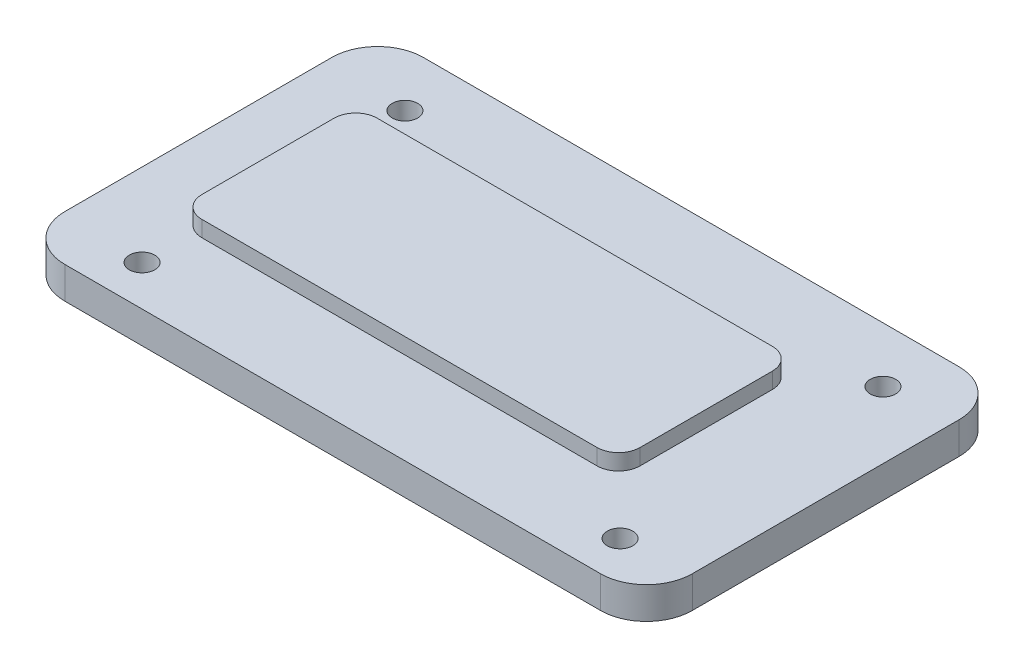
SolidWorks part; units mm, degrees
ref_plane "Front Plane" through (0, 0, 0) normal (0, 0, 1) x (1, 0, 0)
ref_plane "Top Plane" through (0, 0, 0) normal (0, 1, 0) x (1, 0, 0)
ref_plane "Right Plane" through (0, 0, 0) normal (1, 0, 0) x (0, 0, -1)
sketch "Sketch1" plane through (0, 0, 0) normal (0, 1, 0) x (1, 0, 0)
  line L0 (21.25, -8.375) -> (21.25, 8.375)
  line L1 (18.375, 11.25) -> (-15.25, 11.25)
  line L2 (-18.125, 8.375) -> (-18.125, -8.375)
  line L3 (-15.25, -11.25) -> (18.375, -11.25)
  line L4 (-15.25, -11.5) -> (18.375, -11.5)
  line L5 (-18.375, 8.375) -> (-18.375, -8.375)
  line L6 (18.375, 11.5) -> (-15.25, 11.5)
  line L7 (21.5, -8.375) -> (21.5, 8.375)
  line L8 (-15.25, -11.5) -> (18.375, -11.5) construction
  line L9 (-18.375, 8.375) -> (-18.375, -8.375) construction
  line L10 (18.375, 11.5) -> (-15.25, 11.5) construction
  line L11 (21.5, -8.375) -> (21.5, 8.375) construction
  arc A0 (21.25, 8.375) -> (18.375, 11.25) centre (18.375, 8.375) ccw
  arc A1 (-15.25, 11.25) -> (-18.125, 8.375) centre (-15.25, 8.375) ccw
  arc A2 (-18.125, -8.375) -> (-15.25, -11.25) centre (-15.25, -8.375) ccw
  arc A3 (18.375, -11.25) -> (21.25, -8.375) centre (18.375, -8.375) ccw
  arc A4 (-18.375, -8.375) -> (-15.25, -11.5) centre (-15.25, -8.375) ccw
  arc A5 (-15.25, 11.5) -> (-18.375, 8.375) centre (-15.25, 8.375) ccw
  arc A6 (21.5, 8.375) -> (18.375, 11.5) centre (18.375, 8.375) ccw
  arc A7 (18.375, -11.5) -> (21.5, -8.375) centre (18.375, -8.375) ccw
  arc A8 (-18.375, -8.375) -> (-15.25, -11.5) centre (-15.25, -8.375) ccw construction
  arc A9 (-15.25, 11.5) -> (-18.375, 8.375) centre (-15.25, 8.375) ccw construction
  arc A10 (21.5, 8.375) -> (18.375, 11.5) centre (18.375, 8.375) ccw construction
  arc A11 (18.375, -11.5) -> (21.5, -8.375) centre (18.375, -8.375) ccw construction
  dimension "D1" = 0
  dimension "D2" = 0.25
extrude "Boss-Extrude1" add sketch "Sketch1" along normal blind 3
sketch "Sketch2" plane through (0, 3, 0) normal (0, 1, 0) x (1, 0, 0)
  line L0 (14, -4.15) -> (14, 4.15) construction
  line L1 (12.4, 5.75) -> (-12.4, 5.75) construction
  line L2 (18.375, 11.5) -> (-15.25, 11.5) construction
  line L3 (24.5, 12.5) -> (-21.375, 12.5)
  line L4 (21.25, -8.375) -> (21.25, 8.375)
  line L5 (18.375, 11.25) -> (-15.25, 11.25)
  line L6 (-18.125, 8.375) -> (-18.125, -8.375)
  line L7 (-15.25, -11.25) -> (18.375, -11.25)
  line L8 (21.25, -8.375) -> (21.25, 8.375)
  line L9 (18.375, 11.25) -> (-15.25, 11.25)
  line L10 (-18.125, 8.375) -> (-18.125, -8.375)
  line L11 (-15.25, -11.25) -> (18.375, -11.25)
  line L12 (-24.5, 9.375) -> (-24.5, -9.375)
  line L13 (-21.375, -12.5) -> (24.5, -12.5)
  line L14 (24.5, 12.5) -> (-21.375, 12.5)
  line L15 (-24.5, 9.375) -> (-24.5, -9.375)
  line L16 (-21.375, -12.5) -> (24.5, -12.5)
  line L17 (-12.4, -5.75) -> (12.4, -5.75) construction
  line L18 (-14, 4.15) -> (-14, -4.15) construction
  line L19 (14, -4.15) -> (14, 4.15) construction
  line L20 (12.4, 5.75) -> (-12.4, 5.75) construction
  line L21 (18.375, 11.5) -> (-15.25, 11.5)
  line L22 (-12.4, -5.75) -> (12.4, -5.75) construction
  line L23 (-14, 4.15) -> (-14, -4.15) construction
  line L30 (-13.75, 4.15) -> (-13.75, -4.15)
  line L31 (-12.4, -5.5) -> (12.4, -5.5)
  line L32 (13.75, -4.15) -> (13.75, 4.15)
  line L33 (12.4, 5.5) -> (-12.4, 5.5)
  arc A0 (12.4, -5.75) -> (14, -4.15) centre (12.4, -4.15) ccw construction
  arc A1 (-12.4, 5.75) -> (-14, 4.15) centre (-12.4, 4.15) ccw construction
  arc A2 (14, 4.15) -> (12.4, 5.75) centre (12.4, 4.15) ccw construction
  arc A3 (-15.25, 11.5) -> (-18.375, 8.375) centre (-15.25, 8.375) ccw construction
  arc A4 (18.375, -11.25) -> (21.25, -8.375) centre (18.375, -8.375) ccw
  arc A5 (21.25, 8.375) -> (18.375, 11.25) centre (18.375, 8.375) ccw
  arc A6 (-15.25, 11.25) -> (-18.125, 8.375) centre (-15.25, 8.375) ccw
  arc A7 (-18.125, -8.375) -> (-15.25, -11.25) centre (-15.25, -8.375) ccw
  arc A8 (18.375, -11.25) -> (21.25, -8.375) centre (18.375, -8.375) ccw
  arc A9 (21.25, 8.375) -> (18.375, 11.25) centre (18.375, 8.375) ccw
  arc A10 (-15.25, 11.25) -> (-18.125, 8.375) centre (-15.25, 8.375) ccw
  arc A11 (-18.125, -8.375) -> (-15.25, -11.25) centre (-15.25, -8.375) ccw
  arc A12 (-14, -4.15) -> (-12.4, -5.75) centre (-12.4, -4.15) ccw construction
  arc A13 (-21.375, 12.5) -> (-24.5, 9.375) centre (-21.375, 9.375) ccw
  arc A14 (-24.5, -9.375) -> (-21.375, -12.5) centre (-21.375, -9.375) ccw
  arc A15 (24.5, -12.5) -> (27, -7.5) centre (24.5, -9.375) ccw
  arc A16 (27, 7.5) -> (27, -7.5) centre (37, 0) ccw
  arc A17 (27, 7.5) -> (24.5, 12.5) centre (24.5, 9.375) ccw
  arc A18 (-21.375, 12.5) -> (-24.5, 9.375) centre (-21.375, 9.375) ccw
  arc A19 (-24.5, -9.375) -> (-21.375, -12.5) centre (-21.375, -9.375) ccw
  arc A20 (24.5, -12.5) -> (27, -7.5) centre (24.5, -9.375) ccw
  arc A21 (27, 7.5) -> (27, -7.5) centre (37, 0) ccw
  arc A22 (27, 7.5) -> (24.5, 12.5) centre (24.5, 9.375) ccw
  arc A23 (12.4, -5.75) -> (14, -4.15) centre (12.4, -4.15) ccw construction
  arc A24 (-12.4, 5.75) -> (-14, 4.15) centre (-12.4, 4.15) ccw construction
  arc A25 (14, 4.15) -> (12.4, 5.75) centre (12.4, 4.15) ccw construction
  arc A26 (-15.25, 11.5) -> (-18.375, 8.375) centre (-15.25, 8.375) ccw
  arc A27 (-14, -4.15) -> (-12.4, -5.75) centre (-12.4, -4.15) ccw construction
  arc A38 (-13.75, -4.15) -> (-12.4, -5.5) centre (-12.4, -4.15) ccw
  arc A39 (12.4, -5.5) -> (13.75, -4.15) centre (12.4, -4.15) ccw
  arc A40 (13.75, 4.15) -> (12.4, 5.5) centre (12.4, 4.15) ccw
  arc A41 (-12.4, 5.5) -> (-13.75, 4.15) centre (-12.4, 4.15) ccw
  arc M25 (18.375, -11.25) -> (21.25, -8.375) centre (18.375, -8.375) ccw
  line M26 (21.25, -8.375) -> (21.25, 8.375)
  arc M27 (21.25, 8.375) -> (18.375, 11.25) centre (18.375, 8.375) ccw
  line M28 (18.375, 11.25) -> (-15.25, 11.25)
  arc M29 (-15.25, 11.25) -> (-18.125, 8.375) centre (-15.25, 8.375) ccw
  line M30 (-18.125, 8.375) -> (-18.125, -8.375)
  arc M31 (-18.125, -8.375) -> (-15.25, -11.25) centre (-15.25, -8.375) ccw
  line M32 (-15.25, -11.25) -> (18.375, -11.25)
  dimension "D1" = 0
  dimension "D2" = 0
  dimension "D3" = 0.25
extrude "Cut-Extrude1" cut sketch "Sketch2" against normal blind 1 contours A27 L23 A24 L20 A25 L19 A23 L22 M32 M25 M26 M27 M28 M29 M30 M31 region at (20.0873, 3, 10.0873)
sketch "Sketch3" plane through (0, 0, 0) normal (0, -1, 0) x (1, 0, 0)
  line L4 (18.375, 11.25) -> (-15.25, 11.25)
  line L5 (-18.125, 8.375) -> (-18.125, -8.375)
  line L6 (-15.25, -11.25) -> (18.375, -11.25)
  line L7 (21.25, -8.375) -> (21.25, 8.375)
  line L8 (18.375, 11.25) -> (-15.25, 11.25)
  line L9 (-18.125, 8.375) -> (-18.125, -8.375)
  line L10 (-15.25, -11.25) -> (18.375, -11.25)
  line L11 (21.25, -8.375) -> (21.25, 8.375)
  circle A0 centre (-12.9353, 8.721) radius 1.25 construction
  circle A1 centre (-12.9353, -7.779) radius 1.25 construction
  circle A2 centre (17.0647, -7.779) radius 1.25 construction
  circle A3 centre (17.0647, 8.721) radius 1.25 construction
  arc A4 (21.25, 8.375) -> (18.375, 11.25) centre (18.375, 8.375) ccw
  arc A5 (-15.25, 11.25) -> (-18.125, 8.375) centre (-15.25, 8.375) ccw
  arc A6 (-18.125, -8.375) -> (-15.25, -11.25) centre (-15.25, -8.375) ccw
  arc A7 (18.375, -11.25) -> (21.25, -8.375) centre (18.375, -8.375) ccw
  arc A8 (21.25, 8.375) -> (18.375, 11.25) centre (18.375, 8.375) ccw
  arc A9 (-15.25, 11.25) -> (-18.125, 8.375) centre (-15.25, 8.375) ccw
  arc A10 (-18.125, -8.375) -> (-15.25, -11.25) centre (-15.25, -8.375) ccw
  arc A11 (18.375, -11.25) -> (21.25, -8.375) centre (18.375, -8.375) ccw
  circle A12 centre (-12.9353, 8.721) radius 1.25 construction
  circle A13 centre (-12.9353, -7.779) radius 1.25 construction
  circle A14 centre (17.0647, -7.779) radius 1.25 construction
  circle A15 centre (17.0647, 8.721) radius 1.25 construction
  circle A16 centre (17.0647, -7.779) radius 0.8
  circle A17 centre (-12.9353, -7.779) radius 0.8
  circle A18 centre (-12.9353, 8.721) radius 0.8
  circle A19 centre (17.0647, 8.721) radius 0.8
  dimension "D2" = 1.6
  dimension "D3" = 1.6
  dimension "D4" = 1.6
  dimension "D5" = 1.6
  dimension "D1" = 0
extrude "Cut-Extrude2" cut sketch "Sketch3" against normal through all contours A17 | A18 | A16 | A19 | A16 | A19 | A17 region at (17.0647, 0, -7.779) region at (-12.9353, 0, -7.779) region at (-12.9353, 0, 8.721) region at (17.0647, 0, 8.721)
ref_point "Point1"
ref_axis "Axis1" through (-18.125, 2, 11.25) along (0, 1, 0)
ref_point "Machining Origin"
